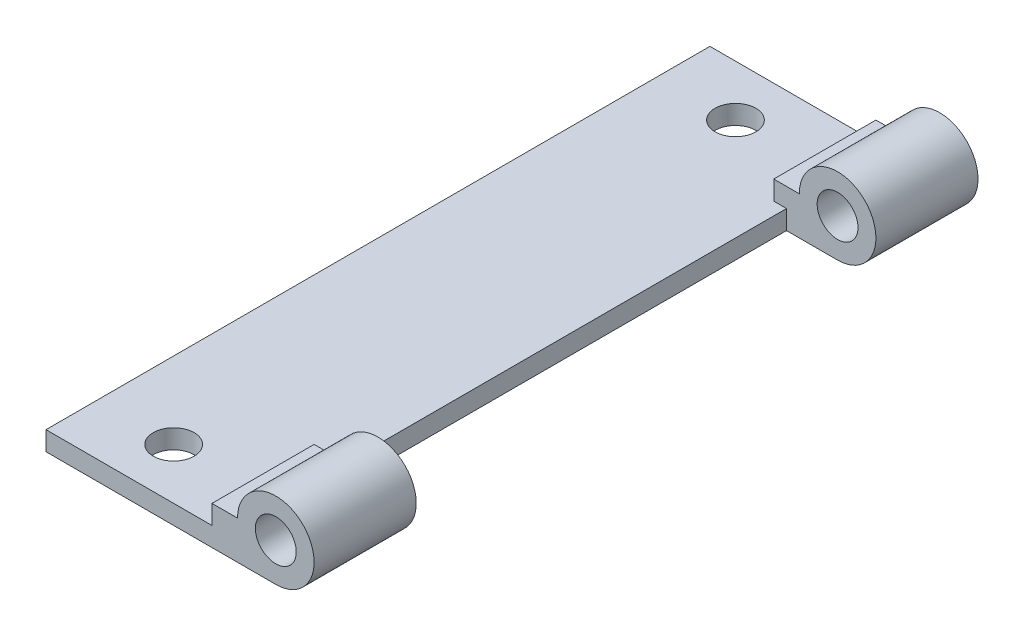
SolidWorks part; units mm, degrees
note: '?' marks a value the reader was unsure of.
ref_plane "前视基准面" through (0, 0, 0) normal (0, 0, 1) x (1, 0, 0)
ref_plane "上视基准面" through (0, 0, 0) normal (0, 1, 0) x (1, 0, 0)
ref_plane "右视基准面" through (0, 0, 0) normal (1, 0, 0) x (0, 0, -1)
other "Configuration Table"
sketch "草图1" plane through (0, 0, 0) normal (0, 0, 1) x (1, 0, 0)
  line L0 (-18, -3) -> (-4, -3)
  line L1 (-4, -3) -> (-4, -1.5)
  line L2 (-4, -1.5) -> (-18, -1.5)
  line L3 (-18, -1.5) -> (-18, -3)
extrude "底板安装脚" add sketch "草图1" along normal blind 52 from offset 26
sketch "草图2" plane through (0, 0, 0) normal (0, 0, 1) x (1, 0, 0)
  line L0 (-5, -3) -> (0, -3)
  line L1 (0, -3) -> (0, 0)
  line L2 (0, 0) -> (-5, 0)
  line L3 (-5, 0) -> (-5, -3)
extrude "外侧铰耳连接" add sketch "草图2" along normal blind 8 from offset 26
sketch "草图3" plane through (0, 0, 0) normal (0, 0, 1) x (1, 0, 0)
  circle A0 centre (0, 0) radius 3
extrude "外侧转轴铰耳" add sketch "草图3" along normal blind 8 from offset 26
sketch "草图4" plane through (0, 0, 0) normal (0, 0, 1) x (1, 0, 0)
  line L0 (-5, -3) -> (0, -3)
  line L1 (0, -3) -> (0, 0)
  line L2 (0, 0) -> (-5, 0)
  line L3 (-5, 0) -> (-5, -3)
extrude "凸台-拉伸4" add sketch "草图4" along normal blind 8 from offset 18
sketch "草图5" plane through (0, 0, 0) normal (0, 0, 1) x (1, 0, 0)
  circle A0 centre (0, 0) radius 3
extrude "凸台-拉伸5" add sketch "草图5" along normal blind 8 from offset 18
sketch "草图6" plane through (0, 0, 0) normal (0, 0, 1) x (1, 0, 0)
  circle A0 centre (0, 0) radius 1.6
extrude "D3p2转轴通孔" cut sketch "草图6" along normal blind 56 from offset 28
sketch "草图7" plane through (0, 0, 0) normal (0, 1, 0) x (1, 0, 0)
  circle A0 centre (-12, 22) radius 1.6
extrude "底板M3安装孔" cut sketch "草图7" along normal blind 100 and the other way blind 100
sketch "草图8" plane through (0, 0, 0) normal (0, 1, 0) x (1, 0, 0)
  circle A0 centre (-12, -22) radius 1.6
extrude "切除-拉伸3" cut sketch "草图8" along normal blind 100 and the other way blind 100
ref_axis "摄像头转轴中心线" through (0, 0, -28.6) along (0, 0, 1)?
